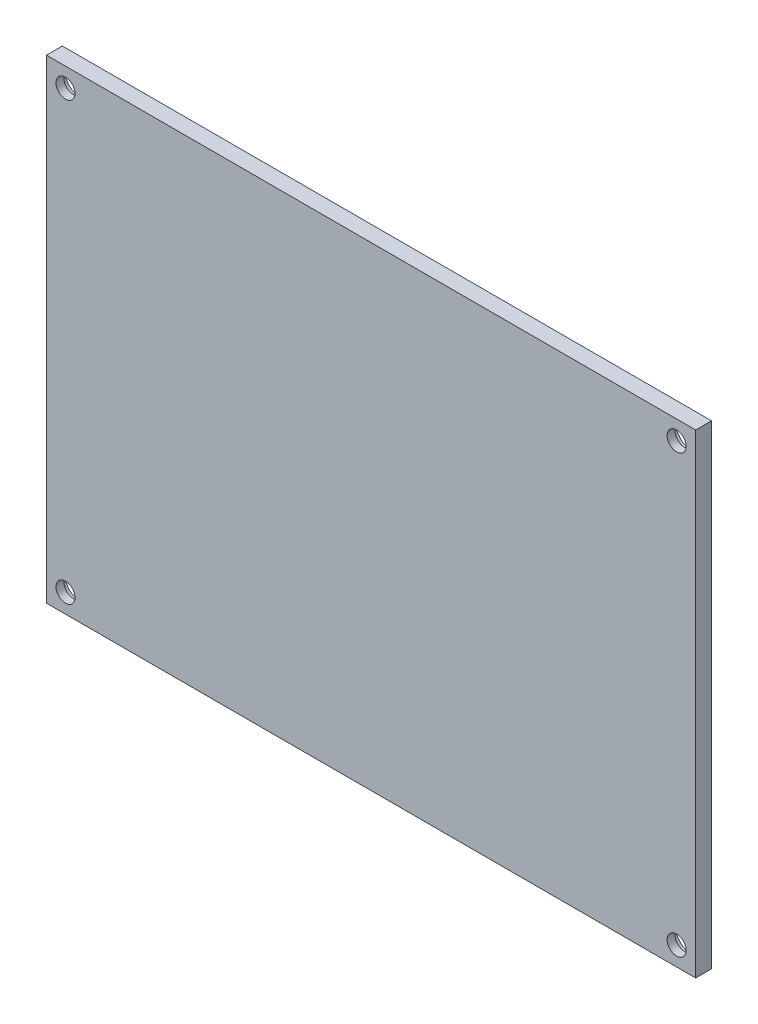
SolidWorks part; units mm, degrees
ref_plane "Front Plane" through (0, 0, 0) normal (0, 0, 1) x (1, 0, 0)
ref_plane "Top Plane" through (0, 0, 0) normal (0, 1, 0) x (1, 0, 0)
ref_plane "Right Plane" through (0, 0, 0) normal (1, 0, 0) x (0, 0, -1)
sketch "Sketch1" plane through (0, 0, 0) normal (0, 0, 1) x (1, 0, 0)
  line L16 (136.4912, -26.7639) -> (136.4912, 33.0361)
  line L17 (54.6912, -26.7639) -> (136.4912, -26.7639)
  line L18 (54.6912, 33.0361) -> (54.6912, -26.7639)
  line L19 (136.4912, 33.0361) -> (54.6912, 33.0361)
  line L20 (136.4912, -26.7639) -> (136.4912, 33.0361)
  line L21 (54.6912, -26.7639) -> (136.4912, -26.7639)
  line L22 (54.6912, 33.0361) -> (54.6912, -26.7639)
  line L23 (136.4912, 33.0361) -> (54.6912, 33.0361)
  dimension "D1" = 0.1
extrude "Boss-Extrude1" add sketch "Sketch1" along normal blind 2
hole_wizard "CBORE for M2 Pan Head Machine Screw1" positions "Sketch4" profile "Sketch3" counterbore size "M2" standard "ANSI Metric"
sketch "Sketch4" plane through (0, 0, 0) normal (0, 0, -1) x (-1, 0, 0)
  point P0 (-134.0912, 30.6361)
  point P3 (-57.0912, 30.6361)
  point P6 (-57.0912, -24.3639)
  point P9 (-134.0912, -24.3639)
sketch "Sketch3" plane through (134.0912, 30.6361, 0) normal (1, 0, 0) x (0, 1, 0)
  line L0 (0, 0) -> (0, 6.721)
  line L1 (0, 6.721) -> (1.2, 6)
  line L2 (1.2, 6) -> (1.2, 1)
  line L3 (1.2, 1) -> (2.125, 1)
  line L4 (2.125, 1) -> (2.125, 0)
  line L5 (2.125, 0) -> (0, 0)
  line L10 (0, 6.721) -> (-1.2, 6) construction
  line L11 (0, -6.35) -> (0, 107.95) construction
  dimension "Hole Dia." = 2.4
  dimension "Hole Depth" = 6
  dimension "C'Bore Dia." = 4.25
  dimension "C'Bore Depth" = 1
  dimension "Drill Angle" = 118
